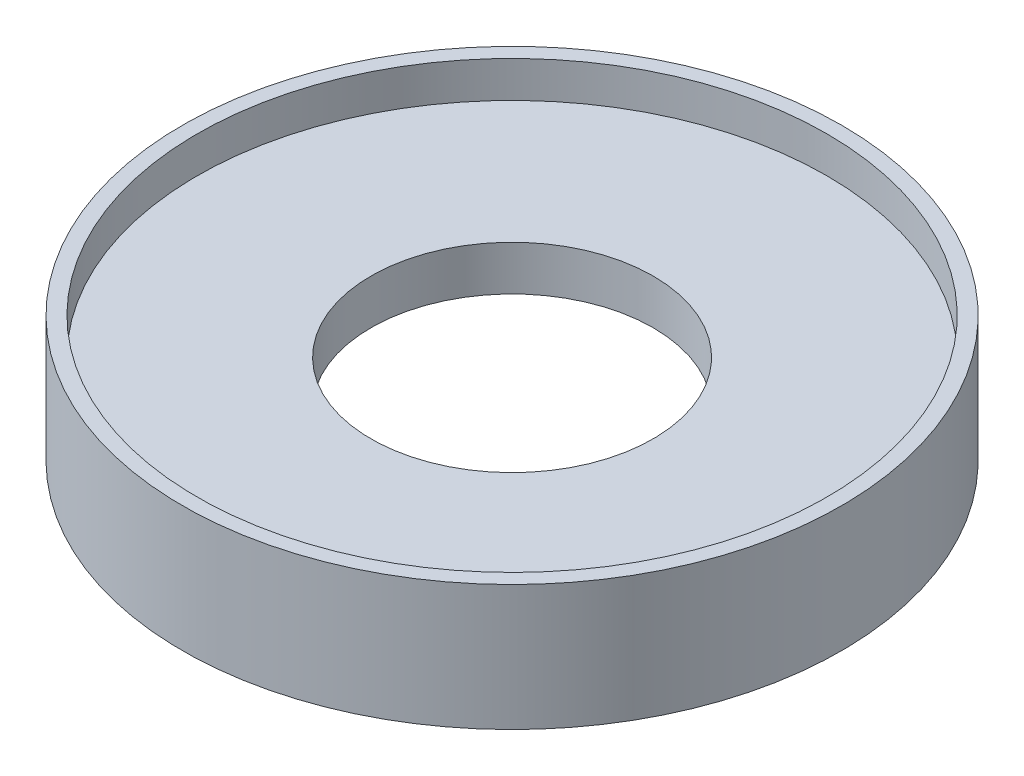
SolidWorks part; units mm, degrees
ref_plane "Front Plane" through (0, 0, 0) normal (0, 0, 1) x (1, 0, 0)
ref_plane "Top Plane" through (0, 0, 0) normal (0, 1, 0) x (1, 0, 0)
ref_plane "Right Plane" through (0, 0, 0) normal (1, 0, 0) x (0, 0, -1)
sketch "Sketch1" plane through (0, 0, 0) normal (1, 0, 0) x (0, 0, -1)
  line L0 (19.05, 0) -> (42.5, 0)
  line L1 (42.5, 0) -> (42.5, -6)
  line L2 (42.5, -6) -> (44.5, -6)
  line L3 (44.5, -6) -> (44.5, 10.96)
  line L4 (44.5, 10.96) -> (42.5, 10.96)
  line L5 (42.5, 10.96) -> (42.5, 6.05)
  line L6 (42.5, 6.05) -> (19.05, 6.05)
  line L7 (19.05, 6.05) -> (19.05, 0)
  line L8 (0, 0) -> (0, 47.8452) construction
  dimension "D1" = 89
  dimension "D2" = 38.1
  dimension "D3" = 85
  dimension "D4" = 6
  dimension "D5" = 6.05
  dimension "D6" = 16.96
revolve "Revolve1" add sketch "Sketch1" angle 360 about L8
ref_point "Point1"
ref_axis "palm_yaw_axis" through (0, 24.7125, 0) along (0, -1, 0)
